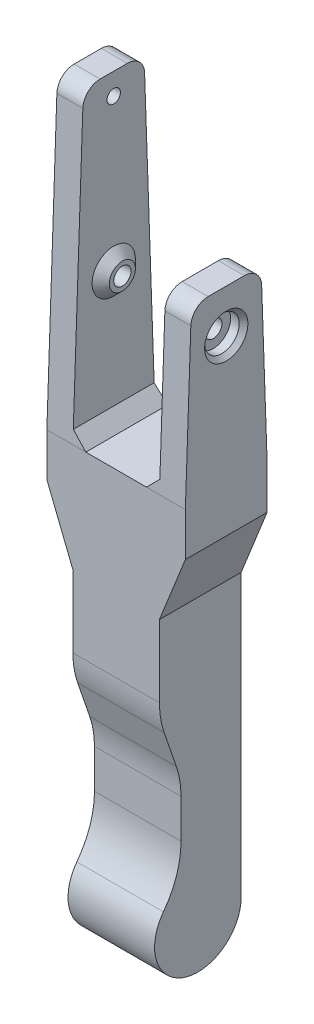
SolidWorks part; units mm, degrees
ref_plane "Front Plane" through (0, 0, 0) normal (0, 0, 1) x (1, 0, 0)
ref_plane "Top Plane" through (0, 0, 0) normal (0, 1, 0) x (1, 0, 0)
ref_plane "Right Plane" through (0, 0, 0) normal (1, 0, 0) x (0, 0, -1)
sketch "Sketch1" plane through (0, 0, 0) normal (1, 0, 0) x (0, 0, -1)
  line L0 (-9.4445, -30) -> (-7, 40)
  line L1 (-7, 40) -> (7, 40)
  line L2 (7, 40) -> (9.4445, -30)
  line L3 (9.4445, -30) -> (-9.4445, -30)
  circle A0 centre (0, 0) radius 2
  point P5 (0, -30)
  point P8 (0, 40)
  dimension "D1" = 4
  dimension "D2" = 40
  dimension "D3" = 92
  dimension "D4" = 30
  dimension "D5" = 14
extrude "Boss-Extrude1" add sketch "Sketch1" along normal blind 6
sketch "Sketch2" plane through (0, 0, 0) normal (-1, 0, 0) x (0, 0, 1)
  circle A0 centre (0, 0) radius 4
  dimension "D1" = 8
extrude "Cut-Extrude1" cut sketch "Sketch2" against normal blind 3
sketch "Sketch3" plane through (0, 0, 0) normal (-1, 0, 0) x (0, 0, 1)
  line L1 (-9.4445, -30) -> (9.4445, -30)
  line L2 (-9.4445, -30) -> (-9.4445, -40)
  line L3 (-9.4445, -40) -> (9.4445, -40)
  line L4 (9.4445, -30) -> (9.4445, -40)
  dimension "D1" = 10
extrude "Boss-Extrude2" add sketch "Sketch3" against normal blind 32
sketch "Sketch4" plane through (32, 0, 0) normal (1, 0, 0) x (0, 0, -1)
  line L0 (9.4445, -30) -> (-9.4445, -30)
  line L1 (-9.4445, -30) -> (-8.0476, 10)
  line L2 (-7, 40) -> (-9.4445, -30) construction
  line L3 (-8.0476, 10) -> (8.0476, 10)
  line L12 (9.4445, -30) -> (7, 40) construction
  line L13 (8.0476, 10) -> (9.4445, -30)
  circle A0 centre (0, 0) radius 2 construction
  circle A1 centre (0, 0) radius 2
  dimension "D1" = 10
extrude "Boss-Extrude3" add sketch "Sketch4" against normal blind 6
fillet "Fillet1" radius 4 4 edges at (3, 40, -7) (3, 40, 7) (29, 10, -8.0476) (29, 10, 8.0476)
extrude "Cut-Extrude2" cut sketch "Sketch2<2>" along normal blind 3 from surface starting at face at (32, -13.2632, 0)
sketch "Sketch2<2>" plane through (0, 0, 0) normal (-1, 0, 0) x (0, 0, 1) same geometry as "Sketch2"
chamfer "Chamfer1" distance 1 angle 45 2 edges at (0, 0, 4) (32, 0, 4)
chamfer "Chamfer2" distance 3 angle 45 2 edges at (6, -30, 0) (26, -30, 0)
sketch "Sketch5" plane through (6, 0, 0) normal (1, 0, 0) x (0, 0, -1)
  circle A0 centre (0, 0) radius 2 construction
  circle A1 centre (0, 0) radius 2
  circle A2 centre (0, 0) radius 3
  dimension "D1" = 1
extrude "Boss-Extrude4" add sketch "Sketch5" along normal blind 2
extrude "Boss-Extrude5" add sketch "Sketch5<2>" against normal blind 2 from surface starting at face at (26, 0, -2)
sketch "Sketch5<2>" plane through (6, 0, 0) normal (1, 0, 0) x (0, 0, -1) same geometry as "Sketch5"
chamfer "Chamfer4" distance 2 angle 45 2 edges at (26, 0, 3) (6, 0, 3)
sketch "Sketch7" plane through (0, 0, -9.4445) normal (0, 0, -1) x (-1, 0, 0)
  line L0 (-32, -40) -> (-26, -55)
  line L1 (-26, -55) -> (-26, -60)
  line L2 (-6, -60) -> (-6, -55)
  line L3 (-6, -55) -> (0, -40)
  line L4 (-6, -60) -> (-26, -60)
  line L5 (-32, -40) -> (0, -40) construction
  line L6 (-16, -60) -> (-16, -40) construction
  line L7 (0, -40) -> (-32, -40)
  dimension "D1" = 20
  dimension "D2" = 5
  dimension "D3" = 15
extrude "Boss-Extrude6" add sketch "Sketch7" against normal up to surface (18.8889 mm away) up to face at (16, -33.3333, 9.4445)
sketch "Sketch8" plane through (26, 0, 0) normal (1, 0, 0) x (0, 0, -1)
  line L1 (9.4445, -60) -> (-9.4445, -60)
  line L2 (-9.4445, -60) -> (-9.4445, -90)
  line L5 (9.4445, -60) -> (9.4445, -120)
  line L6 (-9.4445, -90) -> (-4.4445, -90)
  line L7 (-4.4445, -90) -> (-4.4445, -110.7872)
  arc A2 (-4.4445, -110.7872) -> (9.4445, -120) centre (-0.5555, -120) ccw
  point P10 (9.4445, -90)
  dimension "D1" = 60
  dimension "D2" = 5
  dimension "D3" = 20
extrude "Boss-Extrude7" add sketch "Sketch8" against normal up to surface (20 mm away) up to face at (6, -57.5, 0)
chamfer "Chamfer5" distance 15 angle 19 1 edges at (16, -90, 9.4445) first distance on face at (16, -49, 9.4445)
fillet "Fillet2" radius 20 3 edges at (16, -110.7872, 4.4445) (16, -89.5211, 4.4445) (16, -75, 9.4445)
sketch "Sketch9" plane through (6, 0, 0) normal (1, 0, 0) x (0, 0, -1)
  circle A0 centre (0, 35) radius 1.55
  dimension "D1" = 35
  dimension "D2" = 3.1
extrude "Cut-Extrude3" cut sketch "Sketch9" against normal up to surface (6 mm away) up to face at (0, 0, 5)
sketch "Sketch10" plane through (0, 0, 0) normal (-1, 0, 0) x (0, 0, 1)
  circle A0 centre (0, 35) radius 1.55 construction
  circle A1 centre (0, 35) radius 1.55
  circle A2 centre (0, 35) radius 3.25
  dimension "D1" = 6.5
extrude "Cut-Extrude4" cut sketch "Sketch10" against normal blind 3
chamfer "Chamfer6" distance 1 angle 45 1 edges at (0, 35, 3.25)
